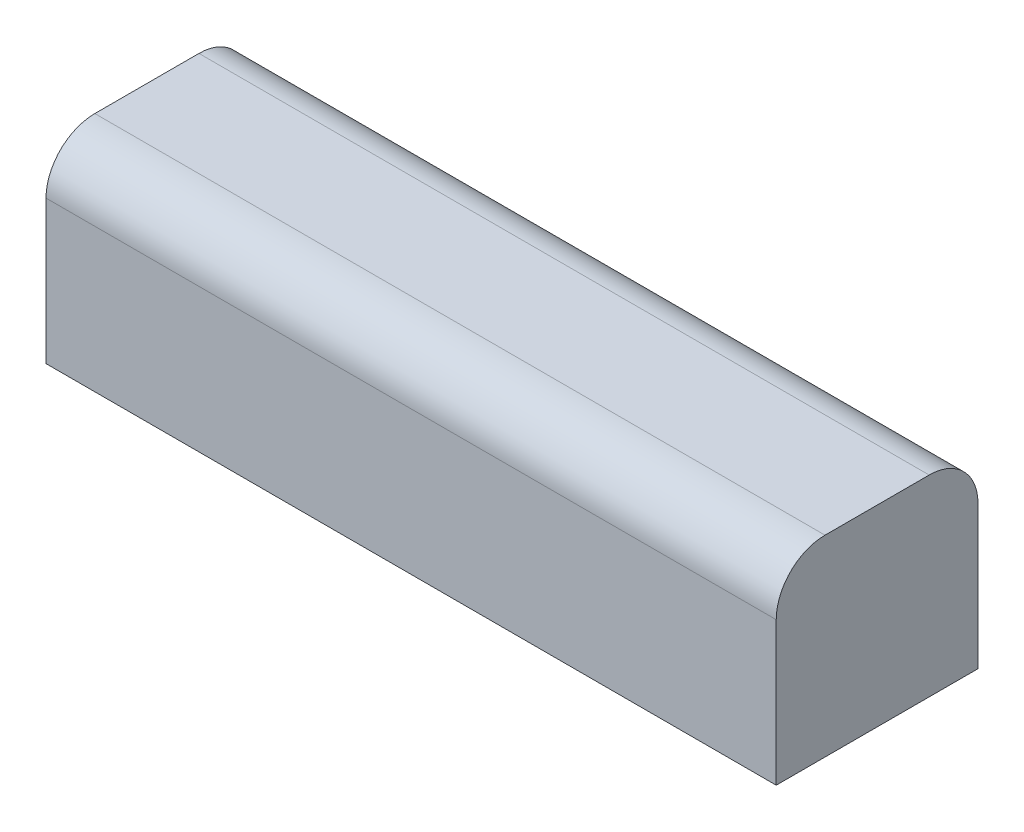
SolidWorks part; units mm, degrees
ref_plane "Front Plane" through (0, 0, 0) normal (0, 0, 1) x (1, 0, 0)
ref_plane "Top Plane" through (0, 0, 0) normal (0, 1, 0) x (1, 0, 0)
ref_plane "Right Plane" through (0, 0, 0) normal (1, 0, 0) x (0, 0, -1)
sketch "Sketch1" plane through (0, 0, 0) normal (0, 1, 0) x (1, 0, 0)
  line L1 (-38, -10.5) -> (38, -10.5)
  line L2 (-38, -10.5) -> (-38, 10.5)
  line L3 (-38, 10.5) -> (38, 10.5)
  line L4 (38, -10.5) -> (38, 10.5)
  line L5 (-38, -10.5) -> (38, 10.5) construction
  line L6 (-38, 10.5) -> (38, -10.5) construction
  point P0 (0, 0)
  dimension "D1" = 76
  dimension "D2" = 21
extrude "Boss-Extrude1" add sketch "Sketch1" along normal blind 20
fillet "Fillet1" radius 5.08 2 edges at (0, 20, -10.5) (0, 20, 10.5)
